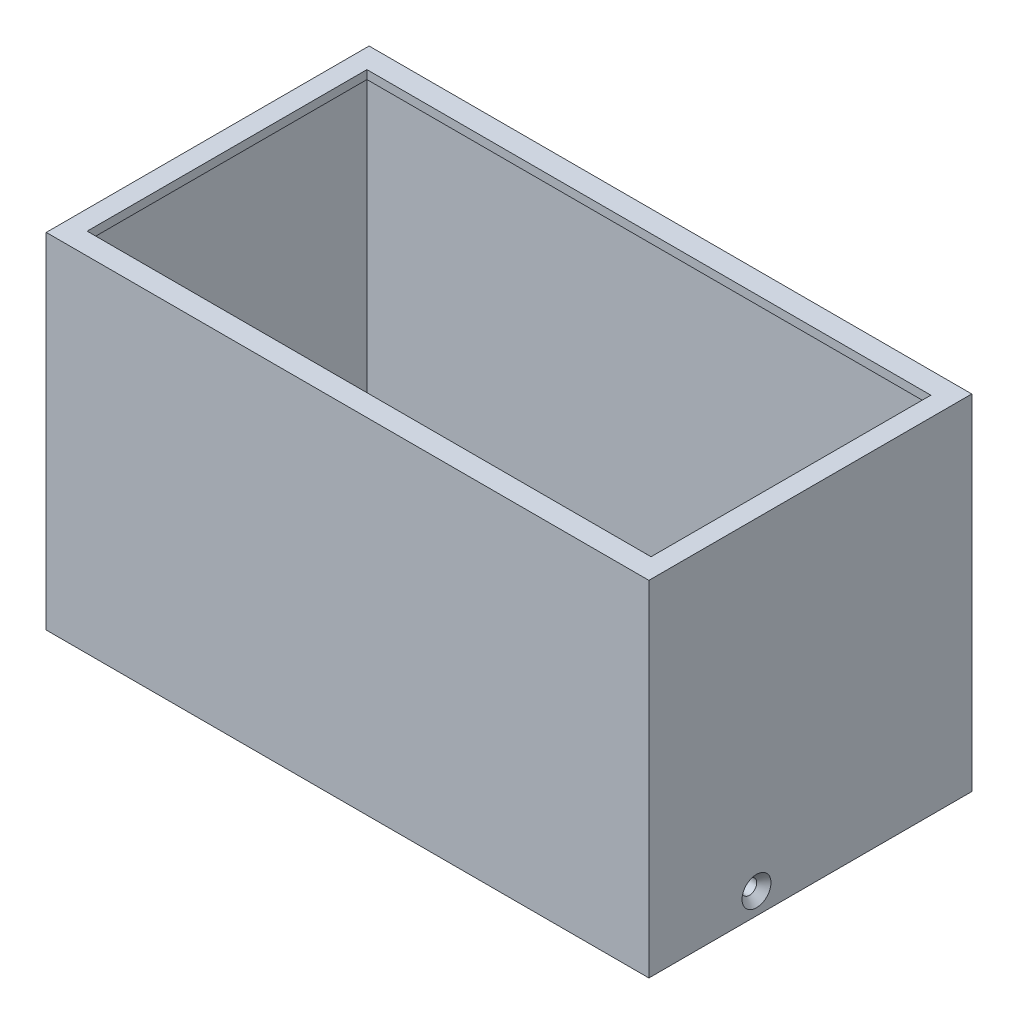
SolidWorks part; units mm, degrees
ref_plane "前视基准面" through (0, 0, 0) normal (0, 0, 1) x (1, 0, 0)
ref_plane "上视基准面" through (0, 0, 0) normal (0, 1, 0) x (1, 0, 0)
ref_plane "右视基准面" through (0, 0, 0) normal (1, 0, 0) x (0, 0, -1)
other "Configuration Table"
sketch "草图1" plane through (0, 0, 0) normal (0, 1, 0) x (1, 0, 0)
  line L1 (70, 37.5) -> (-70, 37.5)
  line L2 (70, 37.5) -> (70, -37.5)
  line L3 (70, -37.5) -> (-70, -37.5)
  line L4 (-70, 37.5) -> (-70, -37.5)
  line L5 (70, 37.5) -> (-70, -37.5) construction
  line L6 (70, -37.5) -> (-70, 37.5) construction
  point P0 (0, 0)
  dimension "D1" = 140
  dimension "D2" = 75
extrude "凸台-拉伸1" add sketch "草图1" along normal blind 80
sketch "草图2" plane through (0, 80, 0) normal (0, 1, 0) x (1, 0, 0)
  line L1 (65.5, 32.5) -> (-65.5, 32.5)
  line L2 (65.5, 32.5) -> (65.5, -32.5)
  line L3 (65.5, -32.5) -> (-65.5, -32.5)
  line L4 (-65.5, 32.5) -> (-65.5, -32.5)
  line L5 (65.5, 32.5) -> (-65.5, -32.5) construction
  line L6 (65.5, -32.5) -> (-65.5, 32.5) construction
  point P0 (0, 0)
  dimension "D1" = 65
  dimension "D2" = 131
extrude "切除-拉伸1" cut sketch "草图2" against normal blind 2
sketch "草图3" plane through (0, 0, 0) normal (0, -1, 0) x (1, 0, 0)
  line L1 (66, 33) -> (-66, 33)
  line L2 (66, 33) -> (66, -33)
  line L3 (66, -33) -> (-66, -33)
  line L4 (-66, 33) -> (-66, -33)
  line L5 (66, 33) -> (-66, -33) construction
  line L6 (66, -33) -> (-66, 33) construction
  point P0 (0, 0)
  dimension "D1" = 66
  dimension "D2" = 132
extrude "切除-拉伸2" cut sketch "草图3" against normal blind 78
sketch "草图4" plane through (-70, 0, 0) normal (-1, 0, 0) x (0, 0, 1)
  line L1 (37.5, 80) -> (37.5, 0) construction
  line L3 (28, 36) -> (28, 44) construction
  line L4 (25.5, 36) -> (25.5, 44)
  line L5 (30.5, 36) -> (30.5, 44)
  arc A0 (25.5, 36) -> (30.5, 36) centre (28, 36) ccw
  arc A1 (30.5, 44) -> (25.5, 44) centre (28, 44) ccw
  point P4 (28, 40)
  point P7 (28.5, 40)
  dimension "D3" = 12
  dimension "D1" = 5
  dimension "D2" = 8
extrude "切除-拉伸3" cut sketch "草图4" against normal blind 10
sketch "草图13" plane through (-70, 0, 0) normal (-1, 0, 0) x (0, 0, 1)
  point P0 (-2.5, 5)
hole_wizard "M3 六角凹锥坑螺钉的锥形沉头孔3" positions "3D草图6" profile "草图14" countersink size "M3" standard "ISO"
sketch3d "3D草图6"
  point P0 (-70, 5, -2.5)
sketch "草图14" plane through (-70, 5, -2.5) normal (0, 1, 0) x (0, 0, 1)
  line L0 (0, 0) -> (0, 7.0215)
  line L1 (0, 7.0215) -> (1.7, 6)
  line L2 (1.7, 6) -> (1.7, 1.66)
  line L3 (1.7, 1.66) -> (3.36, 0)
  line L5 (3.36, 0) -> (0, 0)
  line L6 (-1.7, 1.66) -> (-3.36, 0) construction
  line L10 (0, 7.0215) -> (-1.7, 6) construction
  line L11 (0, -6.35) -> (0, 107.95) construction
  dimension "孔直径" = 3.4
  dimension "孔深度" = 6
  dimension "近端锥形沉头孔直径" = 6.72
  dimension "近端锥形沉头孔角度" = 90
  dimension "导头角度" = 118
sketch "草图16" plane through (70, 0, 0) normal (1, 0, 0) x (0, 0, -1)
  point P0 (-12.5, 5)
hole_wizard "M3 六角凹锥坑螺钉的锥形沉头孔4" positions "3D草图7" profile "草图17" countersink size "M3" standard "ISO"
sketch3d "3D草图7"
  point P0 (70, 5, 12.5)
sketch "草图17" plane through (70, 5, 12.5) normal (0, 1, 0) x (0, 0, -1)
  line L0 (0, 0) -> (0, 7.0215)
  line L1 (0, 7.0215) -> (1.7, 6)
  line L2 (1.7, 6) -> (1.7, 1.66)
  line L3 (1.7, 1.66) -> (3.36, 0)
  line L5 (3.36, 0) -> (0, 0)
  line L6 (-1.7, 1.66) -> (-3.36, 0) construction
  line L10 (0, 7.0215) -> (-1.7, 6) construction
  line L11 (0, -6.35) -> (0, 107.95) construction
  dimension "孔直径" = 3.4
  dimension "孔深度" = 6
  dimension "近端锥形沉头孔直径" = 6.72
  dimension "近端锥形沉头孔角度" = 90
  dimension "导头角度" = 118
sketch "草图18" plane through (0, 0, -37.5) normal (0, 0, -1) x (-1, 0, 0)
  point P0 (15, 5)
hole_wizard "M3 六角凹锥坑螺钉的锥形沉头孔5" positions "3D草图8" profile "草图19" countersink size "M3" standard "ISO"
sketch3d "3D草图8"
  point P0 (-15, 5, -37.5)
sketch "草图19" plane through (-15, 5, -37.5) normal (1, 0, 0) x (0, 1, 0)
  line L0 (0, 0) -> (0, 7.0215)
  line L1 (0, 7.0215) -> (1.7, 6)
  line L2 (1.7, 6) -> (1.7, 1.66)
  line L3 (1.7, 1.66) -> (3.36, 0)
  line L5 (3.36, 0) -> (0, 0)
  line L6 (-1.7, 1.66) -> (-3.36, 0) construction
  line L10 (0, 7.0215) -> (-1.7, 6) construction
  line L11 (0, -6.35) -> (0, 107.95) construction
  dimension "孔直径" = 3.4
  dimension "孔深度" = 6
  dimension "近端锥形沉头孔直径" = 6.72
  dimension "近端锥形沉头孔角度" = 90
  dimension "导头角度" = 118
